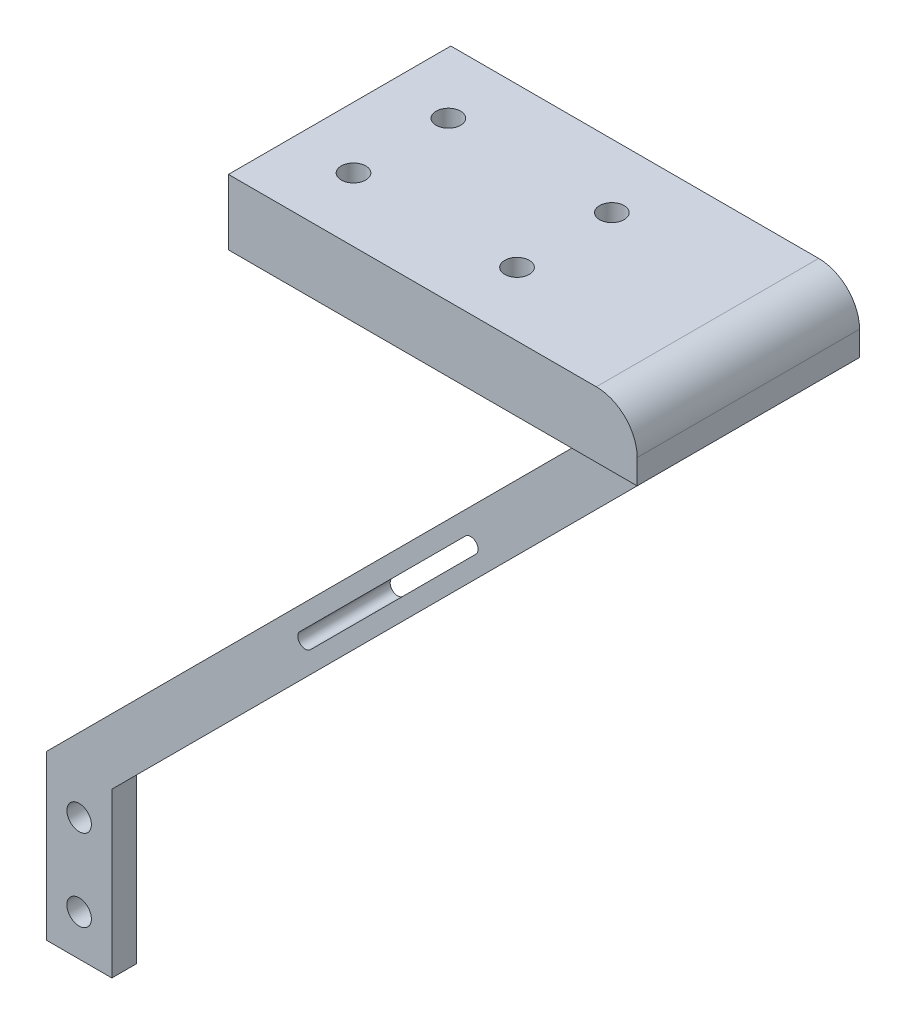
SolidWorks part; units mm, degrees
note: The reader was unsure of these and kept them because the rebuilt part matched: shared geometry of "Croquis1<5>", "Croquis2<4>", "Croquis3<3>".
ref_plane "Alzado" through (0, 0, 0) normal (0, 0, 1) x (1, 0, 0)
ref_plane "Planta" through (0, 0, 0) normal (0, 1, 0) x (1, 0, 0)
ref_plane "Vista lateral" through (0, 0, 0) normal (1, 0, 0) x (0, 0, -1)
sketch "Croquis1" plane through (0, 0, 0) normal (0, 0, 1) x (1, 0, 0)
  line L0 (-22.4906, -992.48) -> (-14.4906, -992.48)
  line L1 (-22.4906, -972.48) -> (48.2201, -901.7693)
  line L2 (-14.4906, -972.48) -> (56.2201, -901.7693)
  line L3 (48.2201, -901.7693) -> (6.2201, -901.7693)
  line L4 (6.2201, -901.7693) -> (6.2201, -899.5193)
  line L5 (6.2201, -893.7693) -> (56.2201, -893.7693)
  line L6 (56.2201, -893.7693) -> (56.2201, -901.7693)
  line L7 (-22.4906, -972.48) -> (-22.4906, -993.48)
  line L8 (-22.4906, -993.48) -> (-34.4906, -993.48)
  line L9 (-34.4906, -993.48) -> (-34.4906, -997.48)
  line L10 (-34.4906, -997.48) -> (-24.4906, -997.48)
  line L11 (-22.4906, -999.48) -> (-22.4906, -1040.48)
  line L12 (-14.4906, -1040.48) -> (-14.4906, -972.48)
  line L13 (-14.4906, -972.48) -> (-22.4906, -972.48)
  line L14 (-22.4906, -972.48) -> (-22.4906, -993.48)
  line L15 (-22.4906, -993.48) -> (-34.4906, -993.48)
  line L16 (-34.4906, -993.48) -> (-34.4906, -997.48)
  line L17 (-34.4906, -997.48) -> (-24.4906, -997.48)
  line L18 (-22.4906, -999.48) -> (-22.4906, -1040.48)
  line L19 (-14.4906, -1040.48) -> (-14.4906, -972.48)
  line L20 (-14.4906, -972.48) -> (-22.4906, -972.48)
  line L21 (6.2201, -897.7693) -> (56.2201, -897.7693) construction
  line L22 (6.2201, -899.5193) -> (56.2201, -899.5193)
  line L23 (6.2201, -896.0193) -> (56.2201, -896.0193)
  line L24 (42.2201, -901.7693) -> (42.2201, -907.7693)
  line L25 (40.2201, -896.0193) -> (40.2201, -899.5193)
  line L26 (6.2201, -896.0193) -> (6.2201, -893.7693)
  line L27 (48.2201, -901.7693) -> (56.4853, -901.7693)
  circle A0 centre (-18.4906, -977.48) radius 1.5 construction
  circle A1 centre (-18.4906, -977.48) radius 1.5
  arc A2 (-22.4906, -999.48) -> (-24.4906, -997.48) centre (-24.4906, -999.48) ccw
  arc A3 (-22.4906, -1040.48) -> (-14.4906, -1040.48) centre (-18.4906, -1040.48) ccw
  arc A4 (-22.4906, -999.48) -> (-24.4906, -997.48) centre (-24.4906, -999.48) ccw
  arc A5 (-22.4906, -1040.48) -> (-14.4906, -1040.48) centre (-18.4906, -1040.48) ccw
  circle A6 centre (-18.4906, -987.48) radius 1.5 construction
  circle A7 centre (-18.4906, -987.48) radius 1.5
  dimension "D4" = 100
  dimension "D5" = 8
  dimension "D2" = 20
  dimension "D3" = 45
  dimension "D8" = 34
  dimension "D9" = 50
  dimension "D10" = 6
  dimension "D1" = 0
  dimension "D6" = 1.75
  dimension "D7" = 1.75
extrude "Saliente-Extruir1" add sketch "Croquis1" along normal blind 3 contours L19 L20 L14 L0 A7 A1 | L27 L1 L20 L2
extrude "Saliente-Extruir2" add sketch "Croquis1<5>" against normal up to vertex (8.3 mm away) contours L27 L1 L20 L2
sketch "Croquis1<5>" plane through (0, 0, 0) normal (0, 0, 1) x (1, 0, 0) same geometry as "Croquis1"
sketch "Croquis2" plane through (-26.2886, -1016.5934, -4.15) normal (0, 0, 1) x (1, 0, 0)
  line L0 (3.798, 44.1134) -> (74.5087, 114.8241) construction
  line L1 (3.798, 44.1134) -> (3.798, 23.1134) construction
  line L2 (3.798, 23.1134) -> (-8.202, 23.1134) construction
  line L3 (-8.202, 23.1134) -> (-8.202, 19.1134) construction
  line L4 (-8.202, 19.1134) -> (1.798, 19.1134) construction
  line L5 (3.798, 17.1134) -> (3.798, -23.8866) construction
  line L6 (11.798, -23.8866) -> (11.798, 44.1134) construction
  line L7 (11.798, 44.1134) -> (3.798, 44.1134) construction
  line L8 (68.5087, 114.8241) -> (68.5087, 108.8241) construction
  line L9 (11.798, 44.1134) -> (82.5087, 114.8241) construction
  line L10 (82.5087, 122.8241) -> (82.5087, 114.8241) construction
  line L11 (32.5087, 122.8241) -> (82.5087, 122.8241) construction
  line L12 (32.5087, 120.5741) -> (32.5087, 122.8241) construction
  line L13 (32.5087, 120.5741) -> (82.5087, 120.5741) construction
  line L14 (74.5087, 114.8241) -> (32.5087, 114.8241) construction
  line L15 (32.5087, 114.8241) -> (32.5087, 117.0741) construction
  line L16 (32.5087, 117.0741) -> (82.5087, 117.0741) construction
  line L17 (74.5087, 114.8241) -> (82.774, 114.8241) construction
  line L18 (3.798, 24.1134) -> (11.798, 24.1134) construction
  line L19 (66.5087, 120.5741) -> (66.5087, 117.0741) construction
  line L20 (3.798, 44.1134) -> (74.5087, 114.8241)
  line L21 (3.798, 44.1134) -> (3.798, 23.1134)
  line L22 (3.798, 23.1134) -> (-8.202, 23.1134)
  line L23 (-8.202, 23.1134) -> (-8.202, 19.1134)
  line L24 (-8.202, 19.1134) -> (1.798, 19.1134)
  line L25 (3.798, 17.1134) -> (3.798, -23.8866)
  line L26 (11.798, -23.8866) -> (11.798, 44.1134)
  line L27 (11.798, 44.1134) -> (3.798, 44.1134)
  line L28 (68.5087, 114.8241) -> (68.5087, 108.8241)
  line L29 (11.798, 44.1134) -> (82.5087, 114.8241)
  line L30 (82.5087, 122.8241) -> (82.5087, 114.8241)
  line L31 (32.5087, 122.8241) -> (82.5087, 122.8241)
  line L32 (32.5087, 120.5741) -> (32.5087, 122.8241)
  line L33 (32.5087, 120.5741) -> (82.5087, 120.5741)
  line L34 (74.5087, 114.8241) -> (32.5087, 114.8241)
  line L35 (32.5087, 114.8241) -> (32.5087, 117.0741)
  line L36 (32.5087, 117.0741) -> (82.5087, 117.0741)
  line L37 (74.5087, 114.8241) -> (82.774, 114.8241)
  line L38 (3.798, 24.1134) -> (11.798, 24.1134)
  line L39 (66.5087, 120.5741) -> (66.5087, 117.0741)
  arc A0 (3.798, 17.1134) -> (1.798, 19.1134) centre (1.798, 17.1134) ccw construction
  circle A1 centre (7.798, 29.1134) radius 1.5
  circle A2 centre (7.798, 29.1134) radius 1.5
  circle A3 centre (7.798, 39.1134) radius 1.5
  circle A4 centre (7.798, 39.1134) radius 1.5
  arc A5 (3.798, -23.8866) -> (11.798, -23.8866) centre (7.798, -23.8866) ccw construction
  arc A6 (3.798, 17.1134) -> (1.798, 19.1134) centre (1.798, 17.1134) ccw
  arc A7 (3.798, -23.8866) -> (11.798, -23.8866) centre (7.798, -23.8866) ccw
  dimension "D1" = 0
  dimension "D2" = 0
extrude "Saliente-Extruir3" add sketch "Croquis2" along normal mid plane 23.2 contours L34 L37 L30 L36 L35 | L33 L39 L36 L30 | L32 L33 L30 L31
extrude "Saliente-Extruir5" add sketch "Croquis2<4>" along normal up to surface and the other way up to surface contours L20 L34 L28 up to face at (-16.9906, -987.48, 3) other way up to face at (16.8647, -937.1247, -8.3)
sketch "Croquis2<4>" plane through (-26.2886, -1016.5934, -4.15) normal (0, 0, 1) x (1, 0, 0) same geometry as "Croquis2"
sketch "Croquis3" plane through (0, -893.7693, 0) normal (0, 1, 0) x (1, 0, 0)
  line L0 (6.2201, 15.75) -> (6.2201, 17.75)
  line L1 (6.2201, 17.75) -> (56.2201, 17.75)
  line L2 (56.2201, 17.75) -> (56.2201, 15.75)
  line L3 (6.2201, 4.15) -> (56.2201, 4.15) construction
  line L4 (56.2201, -9.45) -> (56.2201, -7.45)
  line L5 (6.2201, -9.45) -> (56.2201, -9.45)
  line L6 (6.2201, -7.45) -> (6.2201, -9.45)
  line L7 (56.2201, 15.75) -> (6.2201, 15.75)
  line L8 (6.2201, 15.75) -> (6.2201, -7.45)
  line L9 (6.2201, -7.45) -> (56.2201, -7.45)
  line L10 (56.2201, -7.45) -> (56.2201, 15.75)
  line L11 (56.2201, 15.75) -> (6.2201, 15.75)
  line L12 (6.2201, 15.75) -> (6.2201, -7.45)
  line L13 (6.2201, -7.45) -> (56.2201, -7.45)
  line L14 (56.2201, -7.45) -> (56.2201, 15.75)
  circle A1 centre (13.7201, 9.95) radius 1.5
  circle A2 centre (33.7201, 9.95) radius 1.5
  circle A3 centre (13.7201, -1.65) radius 1.5
  circle A4 centre (33.7201, -1.65) radius 1.5
  point P15 (15.8056, 11.0053)
  point P16 (0, 0)
  point P17 (0, 0)
  point P18 (0, 0)
  line M11 (56.2201, 15.75) -> (6.2201, 15.75)
  line M13 (6.2201, -7.45) -> (56.2201, -7.45)
  dimension "D3" = 3
  dimension "D4" = 20
  dimension "D5" = 7.5
  dimension "D6" = 5.8
  dimension "D2" = 2
  dimension "D1" = 0
extrude "Saliente-Extruir6" add sketch "Croquis3" against normal up to vertex contours L2 L1 L0 M11 | L6 L5 L4 M13
extrude "Cortar-Extruir1" cut sketch "Croquis3<3>" against normal up to surface (8 mm away) contours A3 | A2 | A4 | A1 up to face at (40.2201, -901.7693, -3.4)
sketch "Croquis3<3>" plane through (0, -893.7693, 0) normal (0, 1, 0) x (1, 0, 0) same geometry as "Croquis3"
fillet "Redondeo1" radius 5 1 edges at (56.2201, -893.7693, -4.15)
sketch "Croquis4" plane through (0, 0, -8.3) normal (0, 0, -1) x (-1, 0, 0)
  line L0 (5.3849, -959.4604) -> (-34.619, -919.4565)
  line L1 (-29.4019, -924.6736) -> (-9.1628, -944.9127) construction
  line L2 (-28.7614, -924.0331) -> (-8.5223, -944.2723)
  line L3 (-30.0424, -925.3141) -> (-9.8032, -945.5532)
  line L5 (-42.2201, -901.7693) -> (-56.2201, -901.7693)
  line L6 (-56.2201, -901.7693) -> (14.4906, -972.48)
  line L7 (14.4906, -972.48) -> (22.4906, -972.48)
  line L8 (22.4906, -972.48) -> (-42.2201, -907.7693)
  line L9 (-42.2201, -907.7693) -> (-42.2201, -901.7693)
  line L10 (-42.2201, -901.7693) -> (-56.2201, -901.7693)
  line L11 (-56.2201, -901.7693) -> (14.4906, -972.48)
  line L12 (14.4906, -972.48) -> (22.4906, -972.48)
  line L13 (22.4906, -972.48) -> (-42.2201, -907.7693)
  line L14 (-42.2201, -907.7693) -> (-42.2201, -901.7693)
  arc A0 (-28.7614, -924.0331) -> (-30.0424, -925.3141) centre (-29.4019, -924.6736) ccw
  arc A1 (-9.8032, -945.5532) -> (-8.5223, -944.2723) centre (-9.1628, -944.9127) ccw
  point P9 (-19.2823, -934.7932)
  dimension "D1" = 0
extrude "Cortar-Extruir2" cut sketch "Croquis4" against normal through all contours L0 A1 L2 A0 | L3 A1 L0 A0
